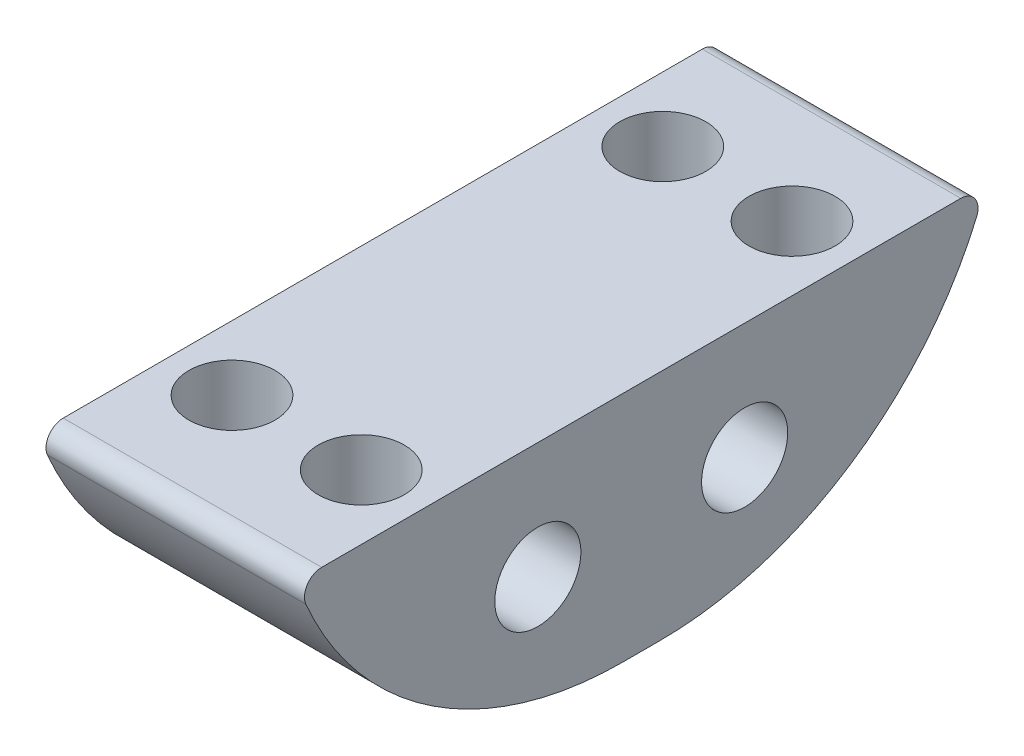
SolidWorks part; units mm, degrees
ref_plane "Front Plane" through (0, 0, 0) normal (0, 0, 1) x (1, 0, 0)
ref_plane "Top Plane" through (0, 0, 0) normal (0, 1, 0) x (1, 0, 0)
ref_plane "Right Plane" through (0, 0, 0) normal (1, 0, 0) x (0, 0, -1)
sketch "Sketch1" plane through (0, 0, 0) normal (0, 1, 0) x (1, 0, 0)
  line L1 (-15, -40) -> (15, -40)
  line L2 (-15, -40) -> (-15, 40)
  line L3 (-15, 40) -> (15, 40)
  line L4 (15, -40) -> (15, 40)
  line L5 (-15, -40) -> (15, 40) construction
  line L6 (-15, 40) -> (15, -40) construction
  point P0 (0, 0)
  dimension "D1" = 30
  dimension "D2" = 80
extrude "Boss-Extrude1" add sketch "Sketch1" along normal blind 27 contours L2 L3 L4 L1
sketch "Sketch2" plane through (15, 0, 0) normal (1, 0, 0) x (0, 0, -1)
  line L0 (-40, 13.5) -> (40, 13.5) construction
  line L1 (-40, 27) -> (-40, 0) construction
  line L2 (40, 27) -> (40, 0) construction
  line L3 (0, 0) -> (0, 27) construction
  line L4 (-40, 27) -> (40, 27) construction
  circle A0 centre (-12, 13.5) radius 5
  circle A1 centre (12, 13.5) radius 5
  dimension "D1" = 12
sketch "Sketch5" plane through (0, 27, 0) normal (0, 1, 0) x (1, 0, 0)
  line L2 (0, -40) -> (0, 40) construction
  line L3 (-15, -40) -> (15, -40) construction
  line L4 (-15, 40) -> (15, 40) construction
  line L5 (-15, 0) -> (15, 0) construction
  line L6 (-15, -40) -> (-15, 40) construction
  line L7 (15, -40) -> (15, 40) construction
  line L9 (-15, -5) -> (15, -5)
  line L10 (-15, -5) -> (-15, 5)
  line L11 (-15, 5) -> (15, 5)
  line L12 (15, -5) -> (15, 5)
  line L13 (-15, -5) -> (15, 5) construction
  line L14 (-15, 5) -> (15, -5) construction
  point P12 (0, 0)
  dimension "D1" = 10
extrude "Cut-Extrude1" cut sketch "Sketch2" against normal blind 40 contours A0 | A1
fillet "Fillet5" radius 40 1 edges at (0, 0, -40)
fillet "Fillet6" radius 40 1 edges at (0, 0, 40)
fillet "Fillet7" radius 2 1 edges at (0, 27, -40)
fillet "Fillet8" radius 2 1 edges at (0, 27, 40)
sketch "Sketch6" plane through (0, 27, 0) normal (0, 1, 0) x (1, 0, 0)
  line L0 (-15, 0) -> (15, 0) construction
  line L1 (-15, 25) -> (0, 25) construction
  line L2 (-15, 5) -> (15, 5) construction
  line L3 (0, 5) -> (0, 40) construction
  line L4 (-15, -37.0856) -> (-15, 37.0856) construction
  line L5 (0, 25) -> (15, 25) construction
  line L6 (15, -37.0856) -> (15, 37.0856) construction
  circle A2 centre (-7.5, 25) radius 5
  circle A3 centre (7.5, 25) radius 5
  circle A4 centre (7.5, -25) radius 5
  circle A5 centre (-7.5, -25) radius 5
  dimension "D1" = 50
  dimension "D2" = 15
extrude "Cut-Extrude3" cut sketch "Sketch6" against normal blind 10
